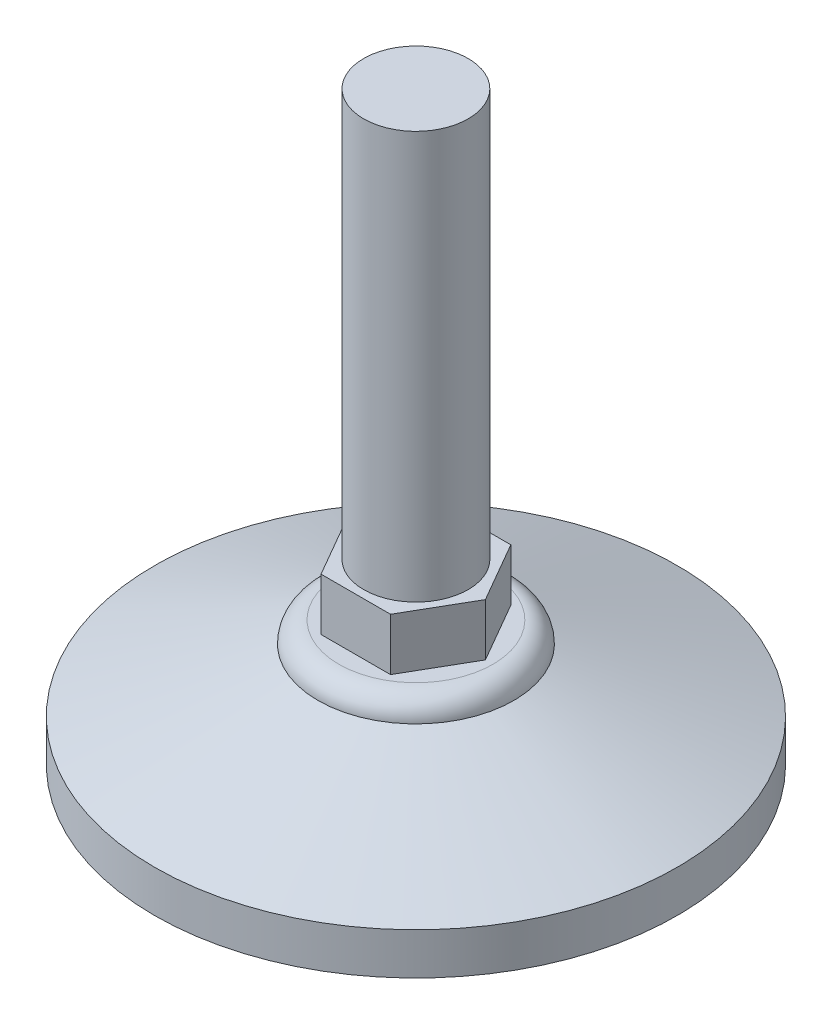
SolidWorks part; units mm, degrees
ref_plane "Front Plane" through (0, 0, 0) normal (0, 0, 1) x (1, 0, 0)
ref_plane "Top Plane" through (0, 0, 0) normal (0, 1, 0) x (1, 0, 0)
ref_plane "Right Plane" through (0, 0, 0) normal (1, 0, 0) x (0, 0, -1)
sketch "Sketch2" plane through (0, 0, 0) normal (0, 1, 0) x (1, 0, 0)
  circle A0 centre (0, 0) radius 25
  dimension "D1" = 50
extrude "Boss-Extrude1" add sketch "Sketch2" along normal blind 4
sketch "Sketch4" plane through (0, 4, 0) normal (0, 1, 0) x (1, 0, 0)
  circle A1 centre (0, 0) radius 25
  circle A2 centre (0, 0) radius 25
  dimension "D1" = 0
extrude "Boss-Extrude2" add sketch "Sketch4" along normal blind 6 draft 69
sketch "Sketch5" plane through (0, 10, 0) normal (0, 1, 0) x (1, 0, 0)
  circle A0 centre (0, 0) radius 9.3695 construction
  circle A1 centre (0, 0) radius 9.3695
extrude "Boss-Extrude3" add sketch "Sketch5" along normal blind 2
sketch "Sketch6" plane through (0, 12, 0) normal (0, 1, 0) x (1, 0, 0)
  circle A0 centre (0, 0) radius 5
  dimension "D1" = 10
extrude "Boss-Extrude4" add sketch "Sketch6" along normal blind 44
fillet "Fillet1" radius 2 1 edges at (0, 12, 9.3695)
sketch "Sketch7" plane through (0, 12, 0) normal (0, 1, 0) x (1, 0, 0)
  line L1 (6.6451, 0) -> (3.3225, 5.7548)
  line L2 (3.3225, 5.7548) -> (-3.3225, 5.7548)
  line L3 (-3.3225, 5.7548) -> (-6.6451, 0)
  line L4 (-6.6451, 0) -> (-3.3225, -5.7548)
  line L5 (-3.3225, -5.7548) -> (3.3225, -5.7548)
  line L6 (3.3225, -5.7548) -> (6.6451, 0)
  circle A0 centre (0, 0) radius 5.7548 construction
  circle A1 centre (0, 0) radius 7.3695 construction
  dimension "D1" = 11.5096
extrude "Boss-Extrude5" add sketch "Sketch7" along normal blind 5
